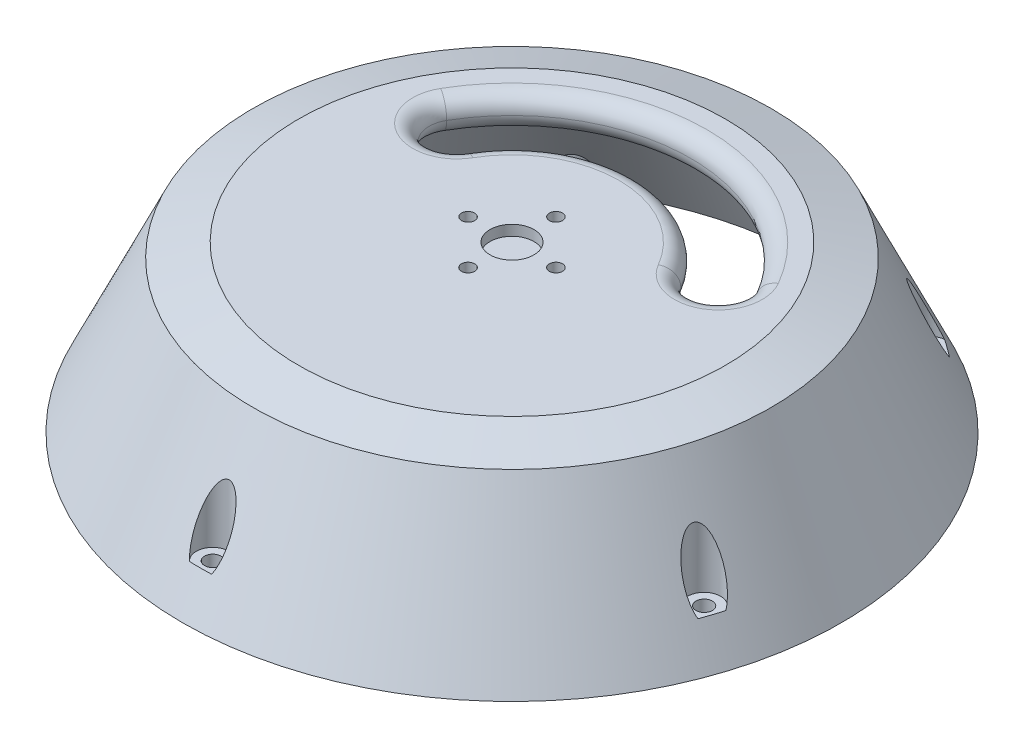
SolidWorks part; units mm, degrees
material "PLA"
ref_plane "Front Plane" through (0, 0, 0) normal (0, 0, 1) x (1, 0, 0)
ref_plane "Top Plane" through (0, 0, 0) normal (0, 1, 0) x (1, 0, 0)
ref_plane "Right Plane" through (0, 0, 0) normal (1, 0, 0) x (0, 0, -1)
sketch "Sketch1" plane through (0, 0, 0) normal (1, 0, 0) x (0, 0, -1)
  line L0 (46.0108, 0) -> (60, -30)
  line L1 (0, 0) -> (46.0108, 0)
  line L2 (0, 0) -> (0, -6)
  line L3 (0, -6) -> (46.0108, -6)
  line L4 (46.0108, 0) -> (46.0108, -6)
  line L5 (60, -30) -> (54.4831, -30)
  line L6 (54.4831, -30) -> (43.2917, -6)
  line L7 (0, -30) -> (60, -30) construction
  line L8 (0, 0) -> (0, -30) construction
  dimension "D1" = 6
  dimension "D2" = 65
  dimension "D3" = 30
  dimension "D4" = 60
  dimension "D6" = 5
revolve "Revolve1" add sketch "Sketch1" angle 360 about L8
sketch "Sketch2" plane through (0, 0, 0) normal (0, 1, 0) x (1, 0, 0)
  line L0 (0, 0) -> (0, 46.0108) construction
  line L1 (0, 0) -> (39.8465, 23.0054) construction
  line L2 (0, 0) -> (-39.8465, 23.0054) construction
  circle A0 centre (0, 0) radius 4
  circle A1 centre (0, 8) radius 1.2
  circle A2 centre (0, 0) radius 4
  circle A3 centre (8, 0) radius 1.2
  circle A4 centre (0, 0) radius 4
  circle A5 centre (0, -8) radius 1.2
  circle A6 centre (0, 0) radius 4
  circle A7 centre (-8, 0) radius 1.2
  circle A8 centre (0, 0) radius 46.0108 construction
  circle A9 centre (0, 0) radius 22.5
  circle A10 centre (0, 0) radius 32.5
  circle A11 centre (23.8157, 13.75) radius 5
  circle A12 centre (-23.8157, 13.75) radius 5
  point P17 (0, 0)
  dimension "D1" = 8
  dimension "D2" = 2.4
  dimension "D3" = 8
  dimension "D5" = 45
  dimension "D6" = 10
  dimension "D7" = 60
  dimension "D8" = 60
  dimension "D4" = 4
extrude "Cut-Extrude1" cut sketch "Sketch2" against normal blind 10 contours A11 | A10 A12 A9 A11 | A12 | A1 | A7 | A3 | A5
sketch "Sketch3" plane through (0, 0, 0) normal (0, 1, 0) x (1, 0, 0)
  circle A0 centre (0, 0) radius 4
  dimension "D1" = 8
extrude "Cut-Extrude2" cut sketch "Sketch3" against normal blind 1.9
ref_plane "Plane1" through (0, -23, 0) normal (0, -1, 0) x (-1, 0, 0)
sketch "Sketch4" plane through (0, -23, 0) normal (0, -1, 0) x (-1, 0, 0)
  line L0 (0, 54.4831) -> (0, -54.4831) construction
  circle A0 centre (0, -54.4831) radius 3
  circle A1 centre (0, 0) radius 54.4831 construction
  dimension "D1" = 6
extrude "Cut-Extrude3" cut sketch "Sketch4" against normal through all
sketch "Sketch5" plane through (0, -30, 0) normal (0, -1, 0) x (1, 0, 0)
  circle A0 centre (0, 54.4831) radius 4
  circle A1 centre (0, 0) radius 54.4831 construction
  dimension "D1" = 8
extrude "Boss-Extrude1" add sketch "Sketch5" against normal up to surface (8.578 mm away)
sketch "Sketch6" plane through (0, -23, 0) normal (0, 1, 0) x (1, 0, 0)
  circle A0 centre (0, -54.4831) radius 1.5
  dimension "D1" = 3
extrude "Cut-Extrude4" cut sketch "Sketch6" against normal through all
pattern_circular "CirPattern1" count 5 over 360 about axis through (0, 0, 0) along (0, 1, 0) of "Cut-Extrude3", "Cut-Extrude4", "Boss-Extrude1"
chamfer "Chamfer3" distance 2.74 distance2 7.15 1 edges at (0, 0, 46.0108)
fillet "Fillet1" radius 3 8 edges at (-26.3157, 0, -9.4199) (-26.3157, -6, -9.4199) (0, -6, -32.5) (0, 0, -32.5) (26.3157, -6, -9.4199) (26.3157, 0, -9.4199) (0, 0, -22.5) (0, -6, -22.5)
fillet "Fillet2" radius 2 1 edges at (0, -6, 43.2917)
